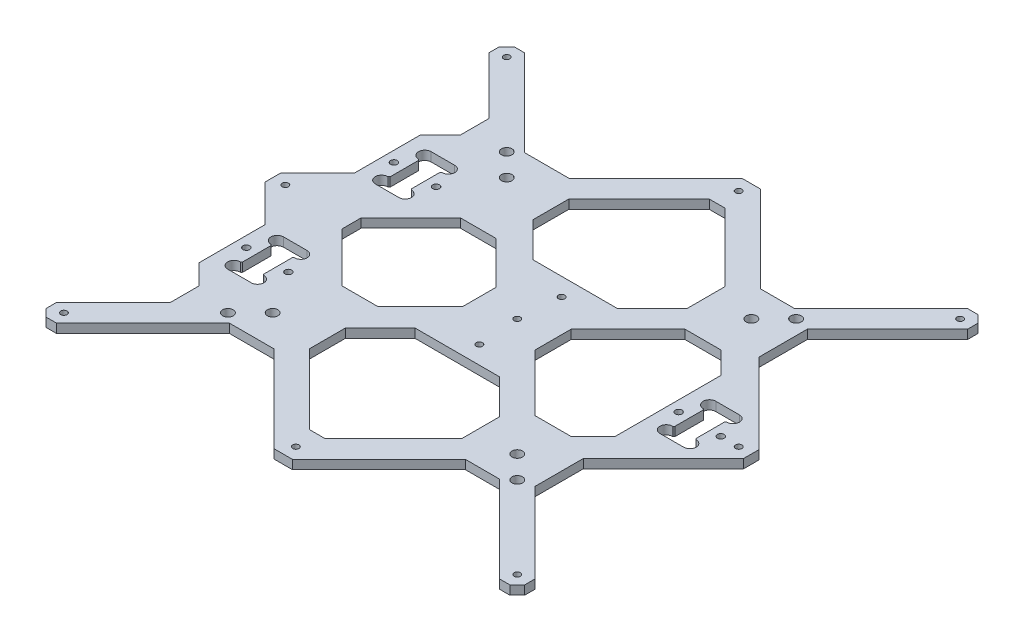
SolidWorks part; units mm, degrees
material "6063-O, Extruded Rod (SS)"
ref_plane "Front Plane" through (0, 0, 0) normal (0, 0, 1) x (1, 0, 0)
ref_plane "Top Plane" through (0, 0, 0) normal (0, 1, 0) x (1, 0, 0)
ref_plane "Right Plane" through (0, 0, 0) normal (1, 0, 0) x (0, 0, -1)
sketch "Sketch2" plane through (0, 0, 0) normal (0, 1, 0) x (1, 0, 0)
  line L0 (162, 177.023) -> (141.977, 157)
  line L1 (141.977, 157) -> (125, 157)
  line L2 (125, 157) -> (101.5, 180.5)
  line L3 (101.5, 189.5) -> (125, 213)
  line L4 (125, 213) -> (141.977, 213)
  line L5 (141.977, 213) -> (162, 192.977)
  line L6 (251.5, 210.0147) -> (240.9853, 220.5294)
  line L7 (240.9853, 220.5294) -> (224.0147, 220.5294)
  line L8 (224.0147, 220.5294) -> (197, 193.5147)
  line L9 (197, 176.4853) -> (224.0147, 149.4706)
  line L10 (224.0147, 149.4706) -> (240.9853, 149.4706)
  line L11 (240.9853, 149.4706) -> (251.5, 159.9853)
  line L12 (184.4001, 296) -> (225.4001, 255)
  line L13 (225.4001, 255) -> (241.5147, 255)
  line L14 (241.5147, 255) -> (282.5147, 296)
  line L15 (282.5147, 296) -> (287.4852, 296)
  line L16 (287.4852, 296) -> (291, 292.4852)
  line L17 (291, 292.4852) -> (291, 287.5147)
  line L18 (291, 287.5147) -> (253, 249.5147)
  line L19 (253, 249.5147) -> (253, 226.667)
  line L20 (253, 226.667) -> (291, 188.667)
  line L21 (291, 188.667) -> (291, 181.333)
  line L22 (291, 181.333) -> (253, 143.333)
  line L23 (253, 143.333) -> (253, 120.4853)
  line L24 (253, 120.4853) -> (291, 82.4853)
  line L25 (291, 82.4853) -> (291, 77.5148)
  line L26 (291, 77.5148) -> (287.4852, 74)
  line L27 (287.4852, 74) -> (282.5147, 74)
  line L28 (282.5147, 74) -> (241.5147, 115)
  line L29 (241.5147, 115) -> (225.4001, 115)
  line L30 (225.4001, 115) -> (184.4001, 74)
  line L31 (184.4001, 74) -> (175.5999, 74)
  line L32 (175.5999, 74) -> (134.5999, 115)
  line L33 (134.5999, 115) -> (113.4853, 115)
  line L34 (113.4853, 115) -> (72.4853, 74)
  line L35 (72.4853, 74) -> (67.5148, 74)
  line L36 (67.5148, 74) -> (64, 77.5148)
  line L37 (64, 77.5148) -> (64, 82.4853)
  line L38 (64, 82.4853) -> (91, 109.4853)
  line L39 (91, 109.4853) -> (91, 123)
  line L40 (91, 123) -> (81.5, 132.5)
  line L41 (81.5, 132.5) -> (81.5, 163.7609)
  line L42 (81.5, 163.7609) -> (64, 181.2609)
  line L43 (64, 188.7391) -> (81.5, 206.2391)
  line L44 (81.5, 206.2391) -> (81.5, 237.5)
  line L45 (81.5, 237.5) -> (91, 247)
  line L46 (91, 247) -> (91, 260.5147)
  line L47 (91, 260.5147) -> (64, 287.5147)
  line L48 (64, 287.5147) -> (64, 292.4852)
  line L49 (64, 292.4852) -> (67.5148, 296)
  line L50 (67.5148, 296) -> (72.4853, 296)
  line L51 (72.4853, 296) -> (113.4853, 255)
  line L52 (113.4853, 255) -> (134.5999, 255)
  line L53 (134.5999, 255) -> (175.5999, 296)
  line L54 (175.5999, 296) -> (184.4001, 296)
  line L55 (143, 246.4158) -> (143, 229.5663)
  line L56 (143, 229.5663) -> (159.5663, 213)
  line L57 (159.5663, 213) -> (199.5147, 213)
  line L58 (199.5147, 213) -> (216, 229.4853)
  line L59 (216, 229.4853) -> (216, 247.4296)
  line L60 (216, 247.4296) -> (183.6826, 279.747)
  line L61 (183.6826, 279.747) -> (176.3174, 279.7332)
  line L62 (176.3174, 279.7332) -> (143, 246.4158)
  line L63 (143, 123.5842) -> (143, 140.4337)
  line L64 (143, 140.4337) -> (159.5663, 157)
  line L65 (159.5663, 157) -> (199.5147, 157)
  line L66 (199.5147, 157) -> (216, 140.5147)
  line L67 (216, 140.5147) -> (216, 122.5704)
  line L68 (216, 122.5704) -> (183.6826, 90.253)
  line L69 (183.6826, 90.253) -> (176.3174, 90.2668)
  line L70 (176.3174, 90.2668) -> (143, 123.5842)
  line L71 (101.5, 226.75) -> (101.5, 213.25)
  line L72 (271.5, 191.75) -> (271.5, 178.25)
  line L73 (101.5, 156.75) -> (101.5, 143.25)
  line L74 (91.5, 226.75) -> (91.5, 213.25)
  line L75 (261.5, 191.75) -> (261.5, 178.25)
  line L76 (91.5, 156.75) -> (91.5, 143.25)
  line L77 (93.6792, 358.4107) -> (93.6792, 347.8262)
  line L78 (93.6792, 347.8262) -> (93.9406, 345.7354)
  line L79 (93.9406, 345.7354) -> (94.4633, 344.2327)
  line L80 (94.4633, 344.2327) -> (95.182, 343.1873)
  line L81 (95.182, 343.1873) -> (96.1846, 341.9648)
  line L82 (96.1846, 341.9648) -> (97.8105, 341.4329)
  line L83 (97.8105, 341.4329) -> (99.6248, 341.0966)
  line L84 (99.6248, 341.0966) -> (101.977, 341.3579)
  line L85 (101.977, 341.3579) -> (104.0024, 342.4033)
  line L86 (104.0024, 342.4033) -> (105.1131, 344.2327)
  line L87 (105.1131, 344.2327) -> (105.5705, 346.7155)
  line L88 (105.5705, 346.7155) -> (105.5705, 349.1983)
  line L89 (105.5705, 349.1983) -> (105.5705, 358.4107)
  line L90 (79.8932, 349.3289) -> (80.0892, 349.3289)
  line L91 (80.0892, 349.3289) -> (81.0039, 348.8063)
  line L92 (81.0039, 348.8063) -> (82.0493, 347.4342)
  line L93 (82.0493, 347.4342) -> (86.4922, 341.0966)
  line L94 (73.5556, 341.1619) -> (73.5556, 358.4107)
  line L95 (73.5556, 358.4107) -> (80.6119, 358.4107)
  line L96 (80.6119, 358.4107) -> (82.768, 357.7574)
  line L97 (82.768, 357.7574) -> (83.8134, 356.7773)
  line L98 (83.8134, 356.7773) -> (84.5321, 355.4706)
  line L99 (84.5321, 355.4706) -> (84.8588, 353.7065)
  line L100 (84.8588, 353.7065) -> (84.5321, 352.0078)
  line L101 (84.5321, 352.0078) -> (83.6827, 350.5703)
  line L102 (83.6827, 350.5703) -> (82.5067, 349.8517)
  line L103 (82.5067, 349.8517) -> (81.3306, 349.525)
  line L104 (81.3306, 349.525) -> (79.8932, 349.3289)
  line L105 (79.8932, 349.3289) -> (78.1291, 349.3289)
  line L106 (78.1291, 349.3289) -> (73.5556, 349.3289)
  line L107 (113.0897, 345.4442) -> (114.2004, 343.4842)
  line L108 (114.2004, 343.4842) -> (116.6178, 341.8507)
  line L109 (116.6178, 341.8507) -> (118.9699, 341.1974)
  line L110 (118.9699, 341.1974) -> (122.4328, 341.7201)
  line L111 (122.4328, 341.7201) -> (124.0662, 343.0268)
  line L112 (124.0662, 343.0268) -> (125.2422, 345.1176)
  line L113 (125.2422, 345.1176) -> (125.2422, 346.359)
  line L114 (125.2422, 346.359) -> (124.9156, 347.4697)
  line L115 (124.9156, 347.4697) -> (123.7395, 348.7764)
  line L116 (123.7395, 348.7764) -> (122.5635, 349.2991)
  line L117 (122.5635, 349.2991) -> (116.7485, 351.0632)
  line L118 (116.7485, 351.0632) -> (115.0497, 352.1739)
  line L119 (115.0497, 352.1739) -> (114.0044, 353.4153)
  line L120 (114.0044, 353.4153) -> (113.8737, 354.5914)
  line L121 (113.8737, 354.5914) -> (114.135, 356.3554)
  line L122 (114.135, 356.3554) -> (115.3764, 357.6622)
  line L123 (115.3764, 357.6622) -> (117.4672, 358.4462)
  line L124 (117.4672, 358.4462) -> (120.0807, 358.5769)
  line L125 (120.0807, 358.5769) -> (122.8248, 357.8582)
  line L126 (122.8248, 357.8582) -> (123.9355, 356.8128)
  line L127 (123.9355, 356.8128) -> (124.3929, 355.5714)
  line L128 (130.9954, 341.0312) -> (137.9864, 358.5414)
  line L129 (137.9864, 358.5414) -> (139.0972, 358.5414)
  line L130 (139.0972, 358.5414) -> (145.9575, 341.0312)
  line L131 (143.9343, 346.1951) -> (133.0803, 346.1927)
  line L132 (55, 341.1619) -> (55, 358.4107)
  line L133 (55, 358.4107) -> (62.0563, 358.4107)
  line L134 (62.0563, 358.4107) -> (64.2125, 357.7574)
  line L135 (64.2125, 357.7574) -> (65.2578, 356.7773)
  line L136 (65.2578, 356.7773) -> (65.9765, 355.4706)
  line L137 (65.9765, 355.4706) -> (66.3032, 353.7065)
  line L138 (66.3032, 353.7065) -> (65.9765, 352.0078)
  line L139 (65.9765, 352.0078) -> (65.1272, 350.5703)
  line L140 (65.1272, 350.5703) -> (63.9511, 349.8517)
  line L141 (63.9511, 349.8517) -> (62.7751, 349.525)
  line L142 (62.7751, 349.525) -> (61.3376, 349.3289)
  line L143 (61.3376, 349.3289) -> (59.5735, 349.3289)
  line L144 (59.5735, 349.3289) -> (55, 349.3289)
  line L145 (251.5, 210.0147) -> (251.5, 159.9853)
  line L146 (197, 193.5147) -> (197, 176.4853)
  line L147 (64, 188.7391) -> (64, 181.2609)
  line L148 (101.5, 189.5) -> (101.5, 180.5)
  line L149 (162, 192.977) -> (162, 177.023)
  line L150 (102.1, 142.75) -> (102, 142.75)
  line L151 (272.1, 177.75) -> (272, 177.75)
  line L152 (102.1, 212.75) -> (102, 212.75)
  line L153 (90.9, 142.75) -> (91, 142.75)
  line L154 (260.9, 177.75) -> (261, 177.75)
  line L155 (90.9, 212.75) -> (91, 212.75)
  line L156 (102, 142.75) -> (101.5, 143.25)
  line L157 (272, 177.75) -> (271.5, 178.25)
  line L158 (102, 212.75) -> (101.5, 213.25)
  line L159 (91, 142.75) -> (91.5, 143.25)
  line L160 (261, 177.75) -> (261.5, 178.25)
  line L161 (91, 212.75) -> (91.5, 213.25)
  line L162 (102.1, 157.25) -> (102, 157.25)
  line L163 (272.1, 192.25) -> (272, 192.25)
  line L164 (102.1, 227.25) -> (102, 227.25)
  line L165 (90.9, 157.25) -> (91, 157.25)
  line L166 (260.9, 192.25) -> (261, 192.25)
  line L167 (90.9, 227.25) -> (91, 227.25)
  line L168 (101.5, 156.75) -> (102, 157.25)
  line L169 (271.5, 191.75) -> (272, 192.25)
  line L170 (101.5, 226.75) -> (102, 227.25)
  line L171 (91.5, 156.75) -> (91, 157.25)
  line L172 (261.5, 191.75) -> (261, 192.25)
  line L173 (91.5, 226.75) -> (91, 227.25)
  line L174 (90.9, 163.25) -> (102.1, 163.25)
  line L175 (260.9, 198.25) -> (272.1, 198.25)
  line L176 (90.9, 233.25) -> (102.1, 233.25)
  line L177 (90.9, 136.75) -> (102.1, 136.75)
  line L178 (260.9, 171.75) -> (272.1, 171.75)
  line L179 (90.9, 206.75) -> (102.1, 206.75)
  arc A0 (102.1, 206.75) -> (102.1, 212.75) centre (102.1, 209.75) ccw
  arc A1 (272.1, 171.75) -> (272.1, 177.75) centre (272.1, 174.75) ccw
  arc A2 (102.1, 136.75) -> (102.1, 142.75) centre (102.1, 139.75) ccw
  arc A3 (90.9, 142.75) -> (90.9, 136.75) centre (90.9, 139.75) ccw
  arc A4 (90.9, 212.75) -> (90.9, 206.75) centre (90.9, 209.75) ccw
  arc A5 (260.9, 177.75) -> (260.9, 171.75) centre (260.9, 174.75) ccw
  arc A6 (102.1, 157.25) -> (102.1, 163.25) centre (102.1, 160.25) ccw
  arc A7 (102.1, 227.25) -> (102.1, 233.25) centre (102.1, 230.25) ccw
  arc A8 (272.1, 192.25) -> (272.1, 198.25) centre (272.1, 195.25) ccw
  arc A9 (90.9, 163.25) -> (90.9, 157.25) centre (90.9, 160.25) ccw
  arc A10 (260.9, 198.25) -> (260.9, 192.25) centre (260.9, 195.25) ccw
  arc A11 (90.9, 233.25) -> (90.9, 227.25) centre (90.9, 230.25) ccw
  circle A12 centre (318.6, 4.9) radius 2.55
  circle A13 centre (318.6, 28.1) radius 2.55
  circle A14 centre (295.4, 28.1) radius 2.55
  circle A15 centre (295.4, 4.9) radius 2.55
  circle A16 centre (281.6, 4.9) radius 2.55
  circle A17 centre (258.4, 4.9) radius 2.55
  circle A18 centre (258.4, 28.1) radius 2.55
  circle A19 centre (281.6, 28.1) radius 2.55
  circle A20 centre (111.6, 4.9) radius 2.55
  circle A21 centre (111.6, 28.1) radius 2.55
  circle A22 centre (88.4, 28.1) radius 2.55
  circle A23 centre (88.4, 4.9) radius 2.55
  circle A24 centre (74.6, 4.9) radius 2.55
  circle A25 centre (74.6, 28.1) radius 2.55
  circle A26 centre (51.4, 28.1) radius 2.55
  circle A27 centre (51.4, 4.9) radius 2.55
  circle A28 centre (360, 39.8) radius 1.5
  circle A29 centre (10, 39.8) radius 1.5
  circle A30 centre (340, 359.8) radius 1.5
  circle A31 centre (30, 39.8) radius 1.5
  circle A32 centre (42.9, 67.8) radius 1.5
  circle A33 centre (340, 39.8) radius 1.5
  circle A34 centre (10, 359.8) radius 1.5
  circle A35 centre (350, 19.8) radius 1.5
  circle A36 centre (47, 99.8) radius 1.5
  circle A37 centre (3.7, 181.1) radius 1.5
  circle A38 centre (20, 19.8) radius 1.5
  circle A39 centre (4.9, 67.8) radius 1.5
  circle A40 centre (360, 359.8) radius 1.5
  circle A41 centre (42.9, 161.8) radius 1.5
  circle A42 centre (3.7, 99.8) radius 1.5
  circle A43 centre (30, 359.8) radius 1.5
  circle A44 centre (47, 174.7) radius 1.5
  circle A45 centre (4.9, 161.8) radius 1.5
  circle A46 centre (46.5, 269.3) radius 1.5
  circle A47 centre (15, 247.8) radius 1.5
  circle A48 centre (3.5, 269.3) radius 1.5
  circle A49 centre (15, 290.8) radius 1.5
  circle A50 centre (180, 80) radius 1.5
  circle A51 centre (180, 290) radius 1.5
  circle A52 centre (285, 80) radius 1.5
  circle A53 centre (70, 290) radius 1.5
  circle A54 centre (285, 290) radius 1.5
  circle A55 centre (70, 185) radius 1.5
  circle A56 centre (180, 185) radius 1.5
  circle A57 centre (285, 185) radius 1.5
  circle A58 centre (256.5, 185) radius 1.6
  circle A59 centre (276.5, 185) radius 1.6
  circle A60 centre (106.5, 220) radius 1.6
  circle A61 centre (106.5, 150) radius 1.6
  circle A62 centre (86.5, 220) radius 1.6
  circle A63 centre (86.5, 150) radius 1.6
  circle A64 centre (70, 80) radius 1.5
  circle A65 centre (181.5, 165.5) radius 1.5
  circle A66 centre (181.5, 204.5) radius 1.5
  circle A67 centre (40, 7) radius 1.6
  circle A68 centre (331, 7) radius 1.6
  circle A69 centre (343, 7) radius 1.6
  circle A70 centre (120, 13) radius 1.6
  circle A71 centre (120, 4) radius 1.6
  circle A72 centre (230, 13) radius 1.6
  circle A73 centre (230, 4) radius 1.6
  circle A74 centre (333.4, 205) radius 2.1
  circle A75 centre (333.4, 88) radius 2.1
  circle A76 centre (26, 7) radius 1.6
  circle A77 centre (153, 13) radius 1.6
  circle A78 centre (153, 4) radius 1.6
  spline S0 degree 2 poles (5, 370) (2.5, 367.5) (0, 365) knots 1472.868668 1472.868668 1472.868668 1479.939736 1479.939736 1479.939736
  spline S1 degree 2 poles (365, 370) (185, 370) (5, 370) knots 1112.868668 1112.868668 1112.868668 1472.868668 1472.868668 1472.868668
  spline S2 degree 2 poles (370, 365) (367.5, 367.5) (365, 370) knots 1105.7976 1105.7976 1105.7976 1112.868668 1112.868668 1112.868668
  spline S3 degree 2 poles (370, 5) (370, 185) (370, 365) knots 745.7976 745.7976 745.7976 1105.7976 1105.7976 1105.7976
  spline S4 degree 2 poles (365, 0) (367.5, 2.5) (370, 5) knots 738.726533 738.726533 738.726533 745.7976 745.7976 745.7976
  spline S5 degree 2 poles (345, 0) (355, 0) (365, 0) knots 718.726533 718.726533 718.726533 738.726533 738.726533 738.726533
  spline S6 degree 2 poles (341, 4) (343, 2) (345, 0) knots 710.241251 710.241251 710.241251 718.726533 718.726533 718.726533
  spline S7 degree 2 poles (333, 4) (337, 4) (341, 4) knots 704.241251 704.241251 704.241251 710.241251 710.241251 710.241251
  spline S8 degree 2 poles (329, 0) (331, 2) (333, 4) knots 698.584397 698.584397 698.584397 704.241251 704.241251 704.241251
  spline S9 degree 2 poles (151, 0) (240, 0) (329, 0) knots 507.584397 507.584397 507.584397 698.584397 698.584397 698.584397
  spline S10 degree 2 poles (146, 5) (148.5, 2.5) (151, 0) knots 501.927543 501.927543 501.927543 507.584397 507.584397 507.584397
  spline S11 degree 2 poles (127, 5) (136.5, 5) (146, 5) knots 487.927543 487.927543 487.927543 501.927543 501.927543 501.927543
  spline S12 degree 2 poles (122, 0) (124.5, 2.5) (127, 5) knots 482.270688 482.270688 482.270688 487.927543 487.927543 487.927543
  spline S13 degree 2 poles (41, 0) (81.5, 0) (122, 0) knots 407.270688 407.270688 407.270688 482.270688 482.270688 482.270688
  spline S14 degree 2 poles (37, 4) (39, 2) (41, 0) knots 401.613834 401.613834 401.613834 407.270688 407.270688 407.270688
  spline S15 degree 2 poles (29, 4) (33, 4) (37, 4) knots 395.613834 395.613834 395.613834 401.613834 401.613834 401.613834
  spline S16 degree 2 poles (25, 0) (27, 2) (29, 4) knots 387.128553 387.128553 387.128553 395.613834 395.613834 395.613834
  spline S17 degree 2 poles (5, 0) (15, 0) (25, 0) knots 367.128553 367.128553 367.128553 387.128553 387.128553 387.128553
  spline S18 degree 2 poles (0, 5) (2.5, 2.5) (5, 0) knots 360.191742 360.191742 360.191742 367.128553 367.128553 367.128553
  spline S19 degree 2 poles (0, 365) (0, 185) (0, 5) knots 0 0 0 360.191742 360.191742 360.191742
  spline S20 degree 2 poles (93, 31.5) (100, 31.5) (107, 31.5) knots 1110.421356 1110.421356 1110.421356 1117.046356 1117.046356 1117.046356
  spline S21 degree 2 poles (88, 36.5) (90.5, 34) (93, 31.5) knots 1103.350288 1103.350288 1103.350288 1110.421356 1110.421356 1110.421356
  spline S22 degree 2 poles (83, 36.5) (85.5, 36.5) (88, 36.5) knots 1098.350288 1098.350288 1098.350288 1103.350288 1103.350288 1103.350288
  spline S23 degree 2 poles (73, 46.5) (78, 41.5) (83, 36.5) knots 1084.208153 1084.208153 1084.208153 1098.350288 1098.350288 1098.350288
  spline S24 degree 2 poles (55, 46.5) (64, 46.5) (73, 46.5) knots 1066.208153 1066.208153 1066.208153 1084.208153 1084.208153 1084.208153
  spline S25 degree 2 poles (50, 51.5) (52.5, 49) (55, 46.5) knots 1059.137085 1059.137085 1059.137085 1066.208153 1066.208153 1066.208153
  spline S26 degree 2 poles (50, 325) (50, 188.25) (50, 51.5) knots 787.637085 787.637085 787.637085 1059.137085 1059.137085 1059.137085
  spline S27 degree 2 poles (55, 330) (52.5, 327.5) (50, 325) knots 780.566017 780.566017 780.566017 787.637085 787.637085 787.637085
  spline S28 degree 2 poles (315, 330) (185, 330) (55, 330) knots 520.566017 520.566017 520.566017 780.566017 780.566017 780.566017
  spline S29 degree 2 poles (320, 325) (317.5, 327.5) (315, 330) knots 513.494949 513.494949 513.494949 520.566017 520.566017 520.566017
  spline S30 degree 2 poles (320, 51.5) (320, 188.25) (320, 325) knots 241.994949 241.994949 241.994949 513.494949 513.494949 513.494949
  spline S31 degree 2 poles (315, 46.5) (317.5, 49) (320, 51.5) knots 234.923882 234.923882 234.923882 241.994949 241.994949 241.994949
  spline S32 degree 2 poles (297, 46.5) (306, 46.5) (315, 46.5) knots 216.923882 216.923882 216.923882 234.923882 234.923882 234.923882
  spline S33 degree 2 poles (287, 36.5) (292, 41.5) (297, 46.5) knots 202.781746 202.781746 202.781746 216.923882 216.923882 216.923882
  spline S34 degree 2 poles (282, 36.5) (284.5, 36.5) (287, 36.5) knots 197.781746 197.781746 197.781746 202.781746 202.781746 202.781746
  spline S35 degree 2 poles (277, 31.5) (279.5, 34) (282, 36.5) knots 190.710678 190.710678 190.710678 197.781746 197.781746 197.781746
  spline S36 degree 2 poles (263, 31.5) (264, 31.5) (265, 31.5) (270, 31.5) (275, 31.5) (276, 31.5) (277, 31.5) knots 176.710678 176.710678 176.710678 178.710678 178.710678 188.710678 188.710678 190.710678 190.710678 190.710678
  spline S37 degree 2 poles (258, 36.5) (260.5, 34) (263, 31.5) knots 169.63961 169.63961 169.63961 176.710678 176.710678 176.710678
  spline S38 degree 2 poles (210, 36.5) (211.75, 36.5) (213.5, 36.5) (235.75, 36.5) (258, 36.5) knots 121.63961 121.63961 121.63961 125.13961 125.13961 169.63961 169.63961 169.63961
  spline S39 degree 2 poles (190, 16.5) (200, 26.5) (210, 36.5) knots 93.355339 93.355339 93.355339 121.63961 121.63961 121.63961
  spline S40 degree 2 poles (180, 16.5) (185, 16.5) (190, 16.5) knots 83.355339 83.355339 83.355339 93.355339 93.355339 93.355339
  spline S41 degree 2 poles (160, 36.5) (170, 26.5) (180, 16.5) knots 55.071068 55.071068 55.071068 83.355339 83.355339 83.355339
  spline S42 degree 2 poles (112, 36.5) (134.25, 36.5) (156.5, 36.5) (158.25, 36.5) (160, 36.5) knots 7.071068 7.071068 7.071068 51.571068 51.571068 55.071068 55.071068 55.071068
  spline S43 degree 2 poles (107, 31.5) (109.5, 34) (112, 36.5) knots 0 0 0 7.071068 7.071068 7.071068
extrude "Boss-Extrude2" add sketch "Sketch2" along normal blind 4.25 contours L43 L147 L42 L41 L40 L39 L38 L37 L36 L35 L34 L33 L32 L31 L30 L29 L28 L27 L26 L25 L24 L23 L22 L21 L20 L19 L18 L17 L16 L15 L14 L13 L12 L54 L53 L52 L51 L50 L49 L48 L47 L46 L45 L44 A66 A65 A64 region at (170.1997, 0, -185)
sketch "Sketch3" plane through (0, 4.25, 0) normal (0, 1, 0) x (1, 0, 0)
  line L0 (181.5, 203) -> (181.5, 206) construction
  line L1 (180, 204.5) -> (183, 204.5) construction
  line L2 (180, 165.5) -> (183, 165.5) construction
  circle A0 centre (181.5, 204.5) radius 1.5 construction
  circle A1 centre (181.5, 204.5) radius 1.5 construction
  circle A2 centre (181.5, 165.5) radius 1.5 construction
ref_plane "Plane1" through (181.5, 0, 0) normal (1, 0, 0) x (0, 0, -1)
ref_plane "Plane2" through (0, 0, -165.5) normal (0, 0, 1) x (1, 0, 0)
ref_plane "Plane3" through (0, 0, -204.5) normal (0, 0, -1) x (-1, 0, 0)
sketch "Sketch4" plane through (0, 4.25, 0) normal (0, 1, 0) x (1, 0, 0)
  line L0 (91, 260.5147) -> (118.7904, 232.7243) construction
  line L2 (241.5147, 255) -> (227.7243, 241.2096) construction
  line L4 (241.5147, 115) -> (227.7243, 128.7904) construction
  line L7 (113.4853, 115) -> (72.4853, 74) construction
  line L8 (127.2757, 128.7904) -> (118.7904, 137.2757) construction
  line L9 (118.7904, 137.2757) -> (91, 109.4853) construction
  line L10 (64, 82.4853) -> (91, 109.4853) construction
  line L11 (67.5148, 74) -> (64, 77.5148) construction
  line L12 (127.2757, 128.7904) -> (113.4853, 115) construction
  line L13 (123.0331, 133.0331) -> (65.7574, 75.7574) construction
  line L14 (227.7243, 128.7904) -> (236.2096, 137.2757) construction
  line L15 (236.2096, 137.2757) -> (253, 120.4853) construction
  line L16 (282.5147, 74) -> (241.5147, 115) construction
  line L17 (291, 77.5148) -> (287.4852, 74) construction
  line L18 (118.7904, 232.7243) -> (127.2757, 241.2096) construction
  line L19 (127.2757, 241.2096) -> (113.4853, 255) construction
  line L20 (91, 260.5147) -> (64, 287.5147) construction
  line L21 (64, 292.4852) -> (67.5148, 296) construction
  line L22 (227.7243, 241.2096) -> (236.2096, 232.7243) construction
  line L23 (236.2096, 232.7243) -> (253, 249.5147) construction
  line L24 (291, 287.5147) -> (253, 249.5147) construction
  line L25 (287.4852, 296) -> (291, 292.4852) construction
  line L26 (123.0331, 236.9669) -> (65.7574, 294.2426) construction
  line L27 (231.9669, 236.9669) -> (289.2426, 294.2426) construction
  line L28 (231.9669, 133.0331) -> (289.2426, 75.7574) construction
  circle A4 centre (119.4975, 129.4975) radius 2.5
  circle A5 centre (108.8909, 118.8909) radius 2.5
  circle A6 centre (108.8909, 251.1091) radius 2.5
  circle A7 centre (119.4975, 240.5025) radius 2.5
  circle A8 centre (235.5025, 240.5025) radius 2.5
  circle A9 centre (246.1091, 251.1091) radius 2.5
  circle A10 centre (235.5025, 129.4975) radius 2.5
  circle A11 centre (246.1091, 118.8909) radius 2.5
  dimension "D4" = 5
  dimension "D7" = 5
  dimension "D8" = 15
  dimension "D10" = 5
  dimension "D11" = 5
  dimension "D14" = 5
  dimension "D15" = 5
  dimension "D18" = 5
  dimension "D19" = 5
  dimension "D2" = 81
  dimension "D3" = 81
  dimension "D5" = 81
  dimension "D6" = 5
  dimension "D9" = 81
  dimension "D12" = 15
  dimension "D13" = 5
  dimension "D16" = 15
  dimension "D17" = 5
  dimension "D20" = 15
  dimension "D21" = 5
extrude "Holes-to-drill" cut sketch "Sketch4" against normal through all
